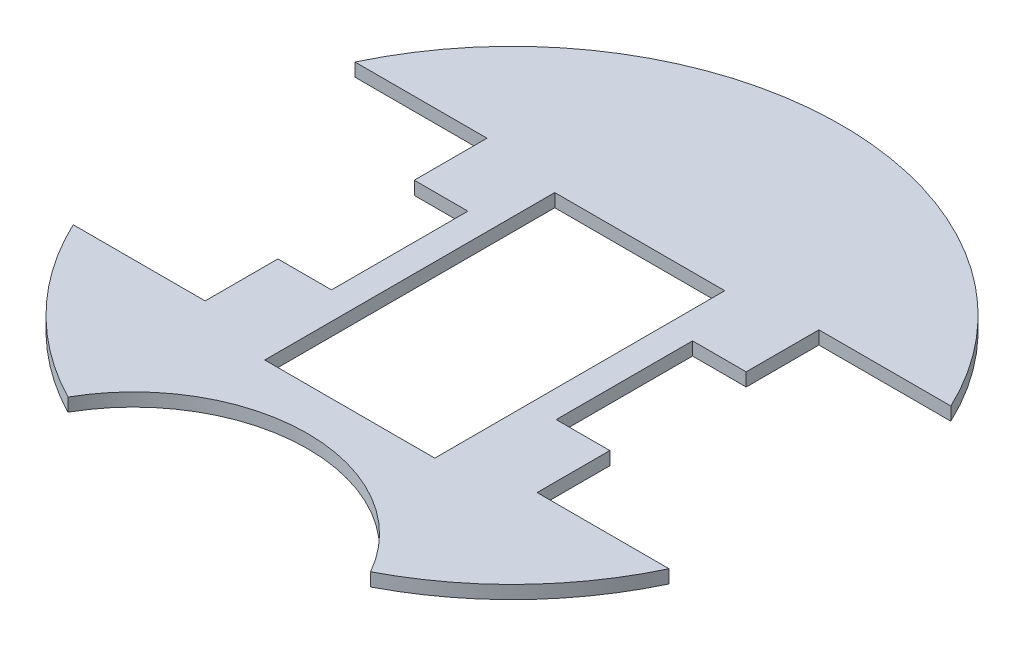
SolidWorks part; units mm, degrees
ref_plane "Front Plane" through (0, 0, 0) normal (0, 0, 1) x (1, 0, 0)
ref_plane "Top Plane" through (0, 0, 0) normal (0, 1, 0) x (1, 0, 0)
ref_plane "Right Plane" through (0, 0, 0) normal (1, 0, 0) x (0, 0, -1)
sketch "Sketch1" plane through (0, 0, 0) normal (0, 1, 0) x (1, 0, 0)
  line L0 (0, -83.2398) -> (-33.2911, -64.4046) construction
  line L1 (0, -83.2398) -> (0, 0) construction
  arc A0 (33.2911, -64.4046) -> (-33.2911, -64.4046) centre (0, 0) ccw
  arc A1 (33.2911, -64.4046) -> (-33.2911, -64.4046) centre (0, -83.2398) ccw
  dimension "D1" = 145
  dimension "D2" = 76.5
  dimension "D3" = 60.5
extrude "Boss-Extrude1" add sketch "Sketch1" along normal blind 2.9
sketch "solenoid placement" plane through (0, 2.9, 0) normal (0, 1, 0) x (1, 0, 0)
  line L4 (-18.7, -35.7) -> (18.7, -35.7)
  line L5 (18.7, -35.7) -> (18.7, 28.1)
  line L6 (18.7, 28.1) -> (-18.7, 28.1)
  line L7 (-18.7, 28.1) -> (-18.7, -35.7)
  line L8 (-18.7, -35.7) -> (18.7, -35.7)
  line L9 (18.7, -35.7) -> (18.7, 28.1)
  line L10 (18.7, 28.1) -> (-18.7, 28.1)
  line L11 (-18.7, 28.1) -> (-18.7, -35.7)
  circle A1 centre (0, 0) radius 72.5 construction
  arc A2 (33.2911, -64.4046) -> (-33.2911, -64.4046) centre (0, 0) ccw construction
  dimension "D1" = 0
extrude "Cut-Extrude1" cut sketch "solenoid placement" against normal through all
sketch "Sketch2" plane through (0, 2.9, 0) normal (0, 1, 0) x (1, 0, 0)
  line L0 (0, 0) -> (0, 72.5) construction
  line L1 (-36.51, -15) -> (-24.71, -15)
  line L2 (36.51, -31) -> (65.5382, -31)
  line L3 (-36.51, 15) -> (-24.71, 15)
  line L4 (-24.71, -15) -> (-24.71, 15)
  line L5 (-36.51, 15) -> (-36.51, 31)
  line L6 (-36.51, 31) -> (-65.5382, 31)
  line L7 (-36.51, -15) -> (-36.51, -31)
  line L8 (-36.51, -31) -> (-65.5382, -31)
  line L9 (36.51, -15) -> (36.51, -31)
  line L10 (36.51, 31) -> (65.5382, 31)
  line L11 (36.51, 15) -> (36.51, 31)
  line L12 (24.71, -15) -> (24.71, 15)
  line L13 (36.51, 15) -> (24.71, 15)
  line L14 (36.51, -15) -> (24.71, -15)
  arc A0 (33.2911, -64.4046) -> (-33.2911, -64.4046) centre (0, 0) ccw construction
  arc A1 (65.5382, 31) -> (65.5382, -31) centre (0, 0) cw
  arc A2 (-65.5382, 31) -> (-65.5382, -31) centre (0, 0) ccw
  dimension "D1" = 62
extrude "Cut-Extrude2" cut sketch "Sketch2" against normal through all
equation "\"smallPulleyTeeth\"= 15"
equation "\"largePulleyTeeth\"= 40"
equation "\"eighthThick\"= 2.9mm"
equation "\"sixteenthThick\" = 1.7mm"
equation "\"quarterThick\"=5.9mm"
equation "\"OD\" = 145mm"
equation "\"puckAngle\" = 60.5deg"
equation "\"D1@Sketch1\"=\"OD\""
equation "\"puckDiam\" = 76.5mm"
equation "\"D2@Sketch1\"=\"puckDiam\""
equation "\"D3@Sketch1\"=\"puckAngle\""
equation "\"D1@Boss-Extrude1\"=\"eighthThick\""
equation "\"axlePress\" = 5.9mm"
equation "\"press\" = 0.2mm"
equation "\"wheelClear\" = 0.3mm"
equation "\"10-32clear\" = 4.5mm"
equation "\"6-32clear\" = 3.3mm"
equation "\"8-32clear\" = 4.0mm"
equation "\"wheelHeight\" = 24mm"
equation "\"wheelWell\" = 62mm"
equation "\"D1@Sketch2\"=\"wheelWell\""
